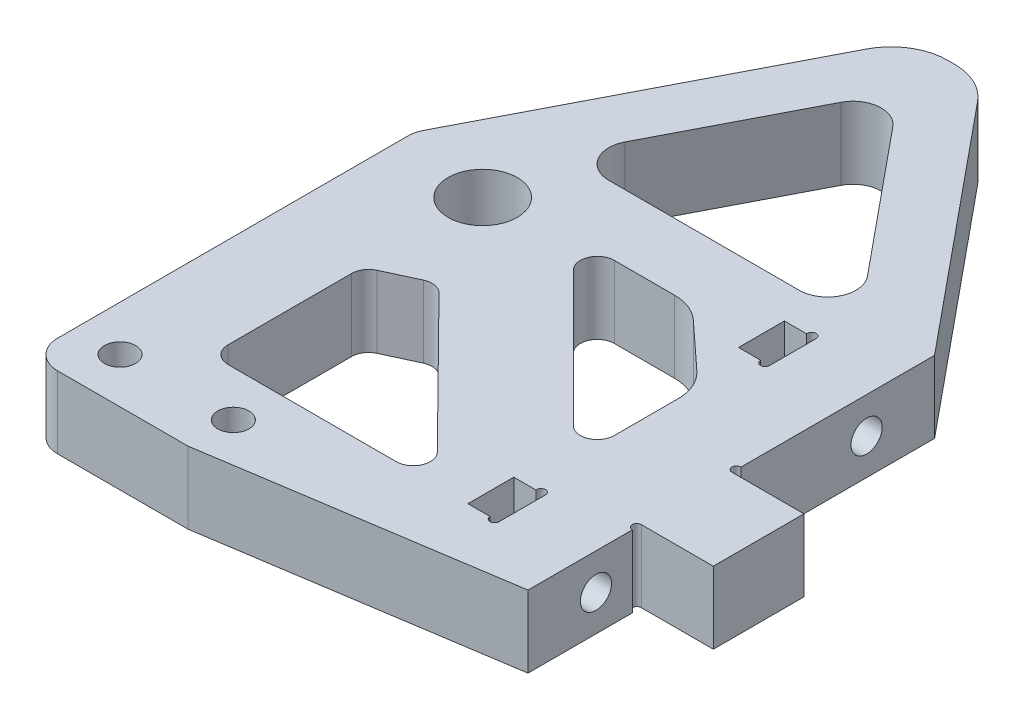
SolidWorks part; units mm, degrees
material "6061 Alloy"
ref_plane "Front Plane" through (0, 0, 0) normal (0, 0, 1) x (1, 0, 0)
ref_plane "Top Plane" through (0, 0, 0) normal (0, 1, 0) x (1, 0, 0)
ref_plane "Right Plane" through (0, 0, 0) normal (1, 0, 0) x (0, 0, -1)
sketch "Sketch1" plane through (0, 0, 0) normal (0, 1, 0) x (1, 0, 0)
  line L1 (-80, 0) -> (-80, 60)
  line L7 (0, 0) -> (-52, -8)
  line L8 (-52, -8) -> (-80, -8)
  line L9 (-80, -8) -> (-80, 0)
  line L10 (-80, 60) -> (-50, 118)
  line L11 (-50, 118) -> (-38, 118)
  line L12 (-38, 118) -> (0, 71.75)
  line L14 (0, 36) -> (12.7, 36)
  line L15 (12.7, 36) -> (12.7, 20)
  line L16 (12.7, 20) -> (0, 20)
  line L18 (0, 18.4) -> (0, 0)
  line L19 (0, 71.75) -> (0, 37.6)
  circle A0 centre (-64, 56) radius 6.1
  circle A3 centre (-72, 0) radius 2.75
  circle A4 centre (-52, 0) radius 2.75
  arc A5 (0, 20) -> (0, 18.4) centre (0, 19.2) ccw
  arc A6 (0, 36) -> (0, 37.6) centre (0, 36.8) cw
  point P23 (12.7, 28)
  dimension "D8" = 12.2
  dimension "D12" = 5.5
  dimension "D16" = 5.5
  dimension "D19" = 0.8
  dimension "D20" = 0.8
  dimension "D1" = 80
  dimension "D2" = 71.75
  dimension "D3" = 60
  dimension "D9" = 16
  dimension "D14" = 8
  dimension "D15" = 20
  dimension "D10" = 8
  dimension "D13" = 8
  dimension "D17" = 56
  dimension "D4" = 58
  dimension "D5" = 30
  dimension "D6" = 12
  dimension "D18" = 12.7
  dimension "D7" = 28
  dimension "D11" = 16
extrude "Boss-Extrude1" add sketch "Sketch1" along normal blind 12.7
fillet "Fillet1" radius 10 2 edges at (-38, 6.35, -118) (-50, 6.35, -118)
sketch "Sketch3" plane through (0, 12.7, 0) normal (0, 1, 0) x (1, 0, 0)
  line L5 (-11.2992, 69.75) -> (-43.4551, 108.8871)
  line L6 (-43.4551, 108.8871) -> (-63.6984, 69.75)
  line L7 (-63.6984, 69.75) -> (-11.2992, 69.75)
  line L10 (0, 71.75) -> (-34.9997, 114.3483) construction
  line L11 (-52.7961, 112.5942) -> (-80, 60) construction
  line L12 (-29.1082, 13.1082) -> (-54.7017, 39.0201)
  line L16 (-80, 60) -> (-80, -8) construction
  line L17 (-63.9447, 34.7442) -> (-63.9447, 8)
  line L18 (-54.7017, 39.0201) -> (-63.9447, 34.7442)
  line L19 (-63.9447, 8) -> (-31.2426, 8)
  line L20 (-42.7574, 58) -> (-32.1279, 58)
  line L21 (-26.7016, 55.8784) -> (-18.5738, 48.3758)
  line L22 (-16, 42.4974) -> (-16, 31.2426)
  line L23 (-21.1213, 29.1213) -> (-44.8787, 52.8787)
  arc A3 (-31.2426, 8) -> (-29.1082, 13.1082) centre (-31.2426, 11) ccw
  arc A4 (-21.1213, 29.1213) -> (-16, 31.2426) centre (-19, 31.2426) ccw
  arc A5 (-44.8787, 52.8787) -> (-42.7574, 58) centre (-42.7574, 55) cw
  arc A6 (-16, 42.4974) -> (-18.5738, 48.3758) centre (-24, 42.4974) ccw
  arc A7 (-26.7016, 55.8784) -> (-32.1279, 58) centre (-32.1279, 50) ccw
  point P19 (-16, 24)
  point P21 (-16, 58)
  point P23 (-50, 58)
  point P24 (-50, 58)
  point P27 (-16, 24)
  point P30 (-24, 8)
  point P31 (-16, 46)
  point P34 (-29, 58)
  point P36 (-58, 42)
  dimension "D8" = 3
  dimension "D9" = 8
  dimension "D1" = 10
  dimension "D2" = 10
  dimension "D3" = 10
  dimension "D4" = 10
  dimension "D5" = 2
  dimension "D6" = 22
  dimension "D7" = 13
  dimension "D10" = 64
  dimension "D11" = 32
  dimension "D12" = 34
  dimension "D13" = 34
extrude "Cut-Extrude1" cut sketch "Sketch3" against normal through all
fillet "Fillet2" radius 5 3 edges at (-43.4551, 6.35, -108.8871) (-11.2992, 6.35, -69.75) (-63.6984, 6.35, -69.75)
sketch "Sketch4" plane through (0, 12.7, 0) normal (0, 1, 0) x (1, 0, 0)
  line L0 (0, 0) -> (0, 18.4) construction
  line L2 (-18.5, 16) -> (-18.5, 7.9)
  line L4 (-13, 16.1) -> (-13, 7.9)
  line L5 (-18.5, 16) -> (-14.5937, 16)
  line L6 (-18.5, 7.9) -> (-14.6, 7.9)
  line L7 (-18.5, 55.65) -> (-14.6, 55.65)
  line L8 (-13, 63.85) -> (-13, 55.65)
  line L9 (-18.5, 63.75) -> (-14.5937, 63.75)
  line L10 (-18.5, 63.75) -> (-18.5, 55.65)
  arc A0 (-13, 16.1) -> (-14.5937, 16) centre (-13.8, 16.1) ccw
  arc A1 (-13, 7.9) -> (-14.6, 7.9) centre (-13.8, 7.9) cw
  arc A2 (-13, 55.65) -> (-14.6, 55.65) centre (-13.8, 55.65) cw
  arc A3 (-13, 63.85) -> (-14.5937, 63.75) centre (-13.8, 63.85) ccw
  point P4 (-13, 12)
  point P12 (-13, 59.75)
  dimension "D5" = 0.8
  dimension "D1" = 12
  dimension "D2" = 13
  dimension "D3" = 8.2
  dimension "D4" = 5.5
  dimension "D7" = 12
  dimension "D6" = 2
extrude "Cut-Extrude2" cut sketch "Sketch4" against normal through all
sketch "Sketch6" plane through (-13, 0, 0) normal (-1, 0, 0) x (0, 0, 1)
  line L0 (-7.9, 0) -> (-7.9, 12.7) construction
  line L1 (-7.9, 12.7) -> (-16.1, 12.7) construction
  line L2 (-55.65, 0) -> (-55.65, 12.7) construction
  circle A0 centre (-12, 6.35) radius 2.75
  circle A1 centre (-59.75, 6.35) radius 2.75
  dimension "D2" = 5.5
  dimension "D5" = 5.5
  dimension "D1" = 4.1
  dimension "D3" = 6.35
  dimension "D4" = 4.1
extrude "Cut-Extrude3" cut sketch "Sketch6" against normal through all
fillet "Fillet3" radius 3 3 edges at (-54.7017, 6.35, -39.0201) (-63.9447, 6.35, -8) (-63.9447, 6.35, -34.7442)
fillet "Fillet4" radius 5 2 edges at (-80, 6.35, 8) (-80, 6.35, -60)
equation "\"DriveMotorLength\"= 90mm"
equation "\"DriveMotorGap\"= 10mm"
equation "\"AluminumThickness\"= 0.5in"
equation "\"ChassisWidth\"= ( \"DriveMotorLength\" + \"AluminumThickness\" ) * 2 + \"DriveMotorGap\""
equation "\"RepeatMagnumHoleWidth\"= 19.05mm"
equation "\"MortiseWidth\"= 16mm"
equation "\"ChassisScrewThruHole\"= 5.5mm"
equation "\"D12@Sketch1\"=\"ChassisScrewThruHole\""
equation "\"D16@Sketch1\"=\"ChassisScrewThruHole\""
equation "\"MortiseSlotWidth\"= 16.2mm"
equation "\"Dogbone\"= 0.8mm"
equation "\"D19@Sketch1\"=\"Dogbone\""
equation "\"D20@Sketch1\"=\"Dogbone\""
equation "\"D5@Sketch4\"=\"Dogbone\""
equation "\"D2@Sketch6\"=\"ChassisScrewThruHole\""
equation "\"D5@Sketch6\"=\"ChassisScrewThruHole\""
equation "\"D11@Sketch1\"=\"MortiseWidth\""
